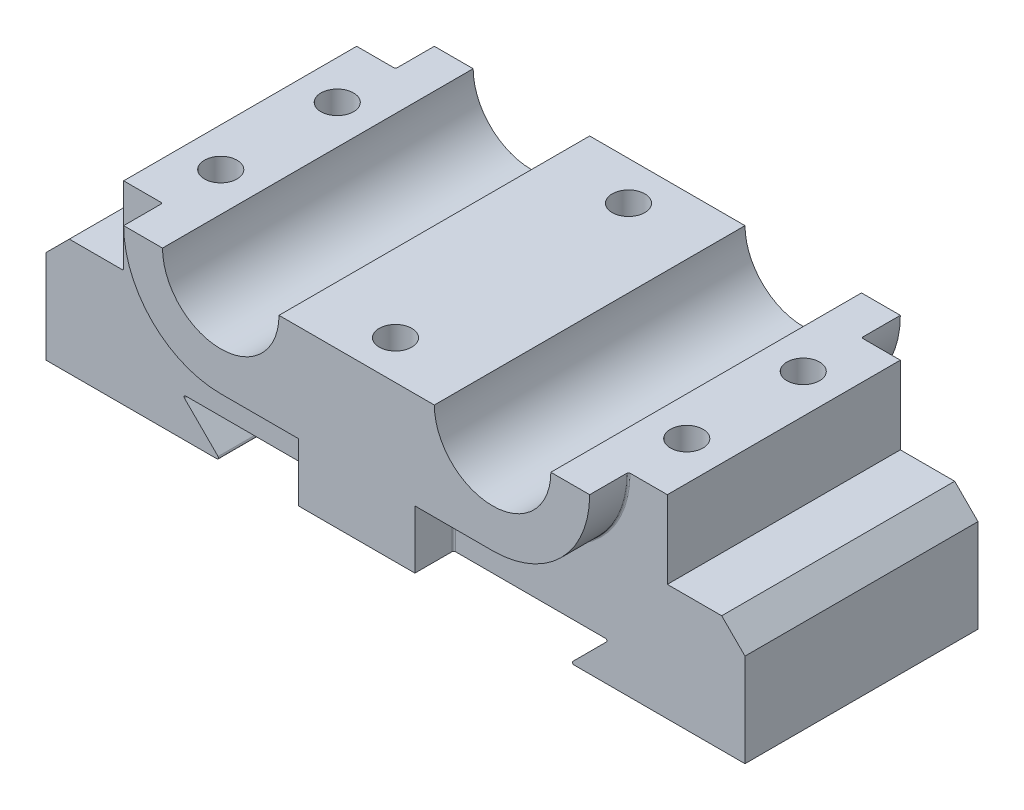
SolidWorks part; units mm, degrees
ref_plane "Спереди" through (0, 0, 0) normal (0, 0, 1) x (1, 0, 0)
ref_plane "Сверху" through (0, 0, 0) normal (0, 1, 0) x (1, 0, 0)
ref_plane "Справа" through (0, 0, 0) normal (1, 0, 0) x (0, 0, -1)
sketch "Эскиз1" plane through (0, 0, 0) normal (0, 0, 1) x (1, 0, 0)
  line L0 (0, 0) -> (17.5, 0) construction
  line L1 (17.5, -12.5) -> (7.5, -12.5)
  line L2 (0, -12.5) -> (0, 0) construction
  line L3 (-10, 0) -> (10, 0)
  line L4 (25, 0) -> (30, 0)
  line L5 (-25, 0) -> (-30, 0)
  line L6 (-7.5, -20) -> (7.5, -20)
  line L7 (7.5, -20) -> (7.5, -12.5)
  line L8 (0, -12.5) -> (0, -20) construction
  line L9 (-7.5, -20) -> (-7.5, -12.5)
  line L10 (-7.5, -12.5) -> (-17.5, -12.5)
  arc A0 (10, 0) -> (25, 0) centre (17.5, 0) ccw
  arc A1 (17.5, -12.5) -> (30, 0) centre (17.5, 0) ccw
  arc A2 (-17.5, -12.5) -> (-30, 0) centre (-17.5, 0) cw
  arc A3 (-10, 0) -> (-25, 0) centre (-17.5, 0) cw
  dimension "D1" = 7.5
  dimension "D2" = 12.5
  dimension "D3" = 17.5
  dimension "D4" = 7.5
  dimension "D5" = 20
extrude "Бобышка-Вытянуть1" add sketch "Эскиз1" along normal blind 20 and the other way blind 20
sketch "Эскиз2" plane through (0, 0, 0) normal (0, 0, 1) x (1, 0, 0)
  line L4 (0, 0) -> (0, -25) construction
  line L14 (10, 0) -> (-10, 0) construction
  line L20 (0, -25) -> (22.5, -25) construction
  line L21 (22.5, -25) -> (45, -25)
  line L33 (45, -25) -> (45, -10)
  line L43 (45, -10) -> (35, -10)
  line L44 (35, -10) -> (35, 0)
  line L50 (35, 0) -> (25, 0)
  line L51 (22.5, -25) -> (27.5, -20)
  line L52 (27.5, -20) -> (-27.5, -20)
  line L53 (-22.5, -25) -> (-27.5, -20)
  line L54 (-22.5, -25) -> (-45, -25)
  line L55 (-45, -25) -> (-45, -10)
  line L56 (-45, -10) -> (-35, -10)
  line L57 (-35, -10) -> (-35, 0)
  line L58 (0, 0) -> (17.5, 0) construction
  line L59 (10, 0) -> (-10, 0)
  line L60 (-25, 0) -> (-35, 0)
  arc A4 (10, 0) -> (25, 0) centre (17.5, 0) ccw
  arc A12 (-10, 0) -> (-25, 0) centre (-17.5, 0) cw
  point P12 (0, -20)
  dimension "D2" = 25
  dimension "D3" = 45
  dimension "D4" = 45
  dimension "D5" = 22.5
  dimension "D6" = 15
  dimension "D7" = 35
  dimension "D1" = 5
extrude "Бобышка-Вытянуть2" add sketch "Эскиз2" along normal blind 15 and the other way blind 15
sketch "Эскиз3" plane through (0, 0, 0) normal (0, 1, 0) x (1, 0, 0)
  line L0 (0, 0) -> (0, -15) construction
  line L1 (0, 0) -> (30, 0) construction
  line L2 (30, 0) -> (30, -7.5) construction
  point P5 (-30, -7.5)
  point P6 (0, -15)
  point P7 (30, -7.5)
  point P8 (30, 7.5)
  point P9 (0, 15)
  point P10 (-30, 7.5)
  dimension "D1" = 30
  dimension "D2" = 15
  dimension "D3" = 7.5
hole_wizard "Отверстие обработанное метчиком M51" positions "Эскиз6" profile "Эскиз7" tap size "M5" standard "ISO"
sketch "Эскиз6" plane through (0, 0, 0) normal (0, 1, 0) x (1, 0, 0)
  point P0 (-30, 7.5)
  point P3 (-30, -7.5)
  point P6 (0, 15)
  point P9 (0, -15)
  point P12 (30, -7.5)
  point P15 (30, 7.5)
sketch "Эскиз7" plane through (-30, 0, -7.5) normal (1, 0, 0) x (0, 0, 1)
  line L0 (0, 0) -> (0, 17.2618)
  line L1 (0, 17.2618) -> (2.1, 16)
  line L2 (2.1, 16) -> (2.1, 0)
  line L5 (2.1, 0) -> (0, 0)
  line L10 (0, 17.2618) -> (-2.1, 16) construction
  line L11 (0, -6.35) -> (0, 107.95) construction
  dimension "Диаметр сверла" = 4.2
  dimension "Глубина сверла" = 16
  dimension "Угол заточки сверла" = 118
cosmetic thread "Отверстие резьбы1" parameters "D1"=10, "D2"=5
cosmetic thread "Отверстие резьбы2" parameters "D1"=10, "D2"=5
cosmetic thread "Отверстие резьбы3" parameters "D1"=10, "D2"=5
cosmetic thread "Отверстие резьбы4" parameters "D1"=10, "D2"=5
cosmetic thread "Отверстие резьбы5" parameters "D1"=10, "D2"=5
cosmetic thread "Отверстие резьбы6" parameters "D1"=10, "D2"=5
chamfer "Фаска1" distance 3 angle 45 2 edges at (45, -10, 0) (-45, -10, 0)
fillet "Скругление1" radius 0.2 4 edges at (22.5, -25, 0) (27.5, -20, 0) (-22.5, -25, 0) (-27.5, -20, 0)
fillet "Скругление2" radius 0.2 1 edges at (-35, -10, 0)
fillet "Скругление3" radius 0.2 12 edges at (12.5, -12.5, -15) (-12.5, -12.5, -15) (26.3388, -8.8388, 15) (-12.5, -12.5, 15) (7.5, -16.25, -15) (26.3388, -8.8388, -15) (-7.5, -16.25, -15) (-26.3388, -8.8388, -15) (12.5, -12.5, 15) (7.5, -16.25, 15) (-7.5, -16.25, 15) (-26.3388, -8.8388, 15)
